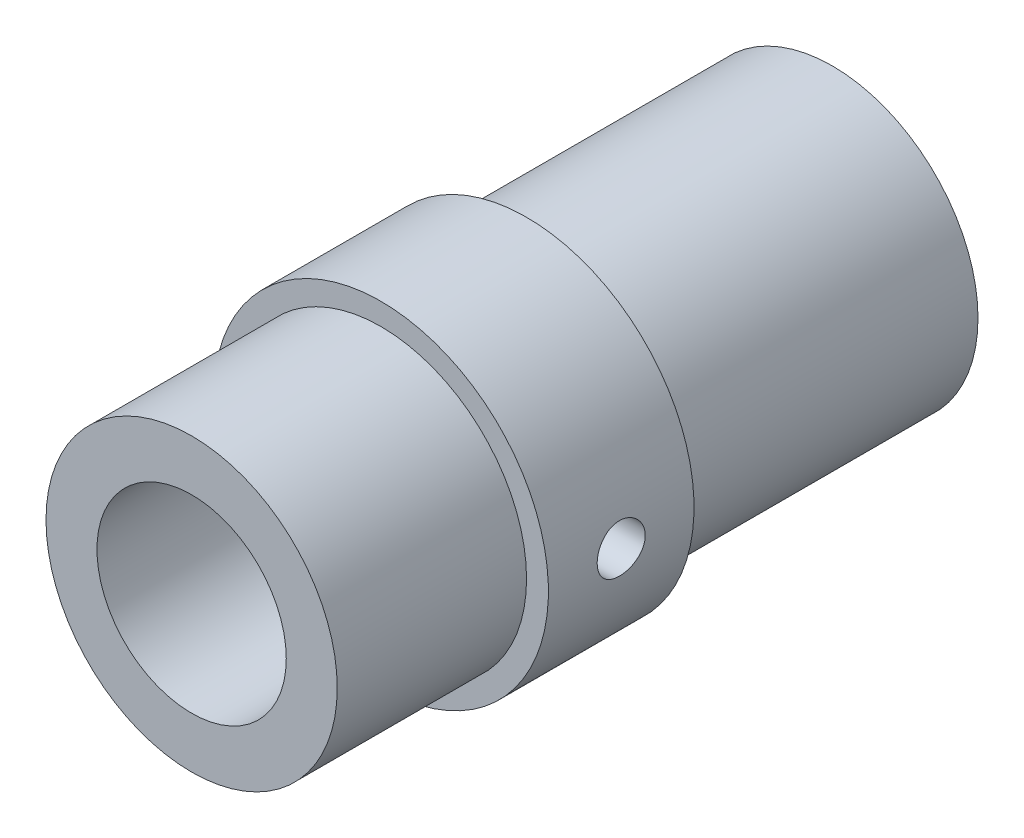
SolidWorks part; units mm, degrees
material "3.1355 (EN-AW 2024)"
ref_plane "Front" through (0, 0, 0) normal (0, 0, 1) x (1, 0, 0)
ref_plane "Top" through (0, 0, 0) normal (0, 1, 0) x (1, 0, 0)
ref_plane "Right" through (0, 0, 0) normal (1, 0, 0) x (0, 0, -1)
sketch "Эскиз1" plane through (0, 0, 0) normal (0, 0, 1) x (1, 0, 0)
  circle A0 centre (0, 0) radius 10
  dimension "D1" = 20
extrude "Бобышка-Вытянуть1" add sketch "Эскиз1" along normal blind 44
sketch "Эскиз2" plane through (0, 0, 44) normal (0, 0, 1) x (1, 0, 0)
  circle A0 centre (0, 0) radius 6.5
  dimension "D1" = 13
extrude "Вырез-Вытянуть1" cut sketch "Эскиз2" against normal blind 27
sketch "Эскиз7" plane through (0, 0, 0) normal (0, 0, -1) x (-1, 0, 0)
  line L0 (-6, 0) -> (0, 0) construction
  line L1 (0, 0) -> (-4.2426, 4.2426) construction
  line L2 (0, 0) -> (4.2426, 4.2426) construction
  line L3 (0, 0) -> (4.2426, -4.2426) construction
  line L4 (0, 0) -> (-4.2426, -4.2426) construction
  circle A0 centre (0, 0) radius 6 construction
  point P11 (0, 0)
  dimension "D1" = 12
  dimension "D2" = 45
  dimension "D3" = 4
hole_wizard "Отверстие обработанное метчиком M3x0.51" positions "Эскиз9" profile "Эскиз8" tap size "M3x0.5" standard "Ansi Metric"
sketch "Эскиз9" plane through (0, 0, 0) normal (0, 0, -1) x (-1, 0, 0)
  point P0 (-4.2426, 4.2426)
  point P3 (4.2426, 4.2426)
  point P6 (4.2426, -4.2426)
  point P9 (-4.2426, -4.2426)
cosmetic thread "Отверстие резьбы2"
cosmetic thread "Отверстие резьбы3"
cosmetic thread "Отверстие резьбы4"
cosmetic thread "Отверстие резьбы5"
sketch "Эскиз8" plane through (4.2426, 4.2426, 0) normal (1, 0, 0) x (0, 1, 0)
  line L0 (0, 0) -> (0, 9.2511)
  line L1 (0, 9.2511) -> (1.25, 8.5)
  line L2 (1.25, 8.5) -> (1.25, 0)
  line L5 (1.25, 0) -> (0, 0)
  line L10 (0, 9.2511) -> (-1.25, 8.5) construction
  line L11 (0, -6.35) -> (0, 107.95) construction
  dimension "Диаметр сверла" = 2.5
  dimension "Глубина сверла" = 8.5
  dimension "Угол заточки сверла" = 118
ref_plane "Плоскость2" through (0, 0, 21) normal (0, 0, -1) x (-1, 0, 0)
sketch "Эскиз10" plane through (0, 0, 21) normal (0, 0, -1) x (-1, 0, 0)
  circle A0 centre (0, 0) radius 11.5
  circle A1 centre (0, 0) radius 10
  circle A2 centre (0, 0) radius 10 construction
  dimension "D1" = 23
extrude "Бобышка-Вытянуть2" add sketch "Эскиз10" against normal blind 10
sketch "Эскиз3" plane through (0, 0, 0) normal (0, 1, 0) x (1, 0, 0)
  line L0 (-11.5, -31) -> (-11.5, -26) construction
  dimension "D1" = 5
ref_plane "Плоскость1" through (-11.5, 0, 0) normal (1, 0, 0) x (0, 0, -1)
hole_wizard "Отверстие обработанное метчиком M4x0.71" positions "Эскиз5" profile "Эскиз4" tap size "M4x0.7" standard "Ansi Metric" end condition through all
sketch "Эскиз5" plane through (-11.5, 0, 0) normal (1, 0, 0) x (0, 0, -1)
  line L0 (-31, 0) -> (-26, 0) construction
  point P0 (-26, 0)
cosmetic thread "Отверстие резьбы9"
sketch "Эскиз4" plane through (-11.5, 0, 26) normal (0, 1, 0) x (0, 0, 1)
  line L0 (0, 0) -> (0, 23)
  line L1 (0, 23) -> (1.65, 23)
  line L2 (1.65, 23) -> (1.65, 0)
  line L5 (1.65, 0) -> (0, 0)
  line L11 (0, -6.35) -> (0, 107.95) construction
  dimension "Диаметр проходного сверла" = 3.3
  dimension "Глубина проходного сверла" = 23
